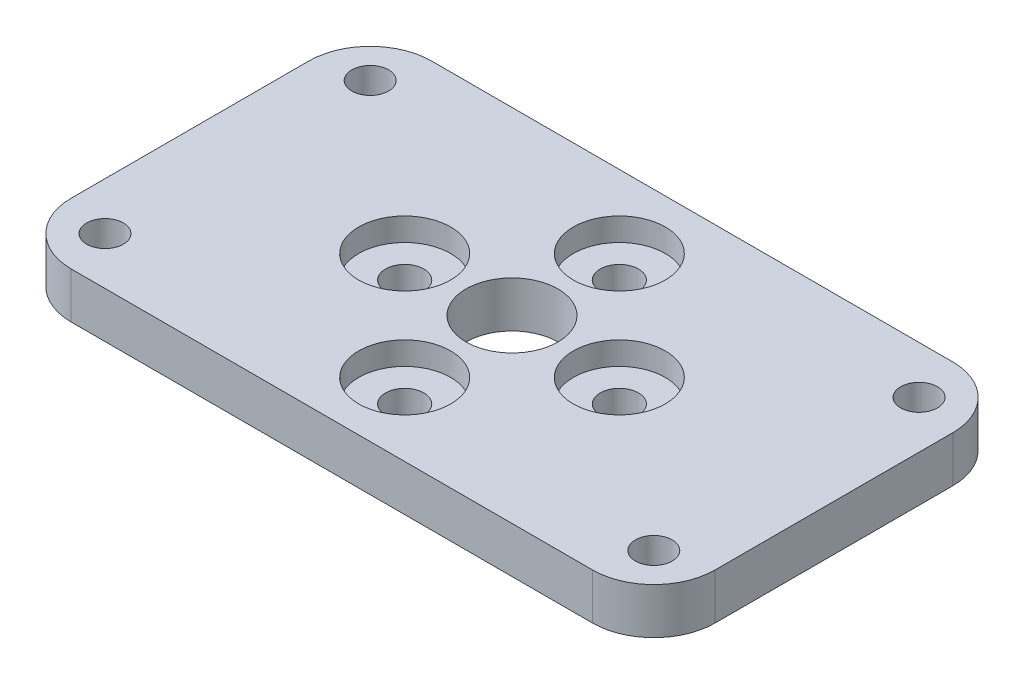
SolidWorks part; units mm, degrees
ref_plane "前视基准面" through (0, 0, 0) normal (0, 0, 1) x (1, 0, 0)
ref_plane "上视基准面" through (0, 0, 0) normal (0, 1, 0) x (1, 0, 0)
ref_plane "右视基准面" through (0, 0, 0) normal (1, 0, 0) x (0, 0, -1)
other "Configuration Table"
sketch "草图1" plane through (0, 0, 0) normal (0, 1, 0) x (1, 0, 0)
  line L0 (-13.2993, 0) -> (13.5934, 0) construction
  line L1 (0, 16.6571) -> (0, -12.7411) construction
  line L3 (21, -11.75) -> (-21, -11.75)
  line L4 (21, -11.75) -> (21, 11.75)
  line L5 (21, 11.75) -> (-21, 11.75)
  line L6 (-21, -11.75) -> (-21, 11.75)
  line L7 (21, -11.75) -> (-21, 11.75) construction
  line L8 (21, 11.75) -> (-21, -11.75) construction
  circle A0 centre (0, 0) radius 7 construction
  circle A1 centre (7, 0) radius 1.25
  circle A2 centre (0, -7) radius 1.25
  circle A3 centre (-7, 0) radius 1.25
  circle A4 centre (0, 7) radius 1.25
  circle A5 centre (-17.9, 8.65) radius 1.2
  circle A6 centre (17.9, 8.65) radius 1.2
  circle A7 centre (-17.9, -8.65) radius 1.2
  circle A8 centre (17.9, -8.65) radius 1.2
  circle A9 centre (0, 0) radius 3
  point P18 (0, 0)
  dimension "D1" = 14
  dimension "D2" = 2.5
  dimension "D4" = 35.8
  dimension "D5" = 17.3
  dimension "D6" = 2.4
  dimension "D7" = 42
  dimension "D8" = 23.5
  dimension "D3" = 4
extrude "凸台-拉伸1" add sketch "草图1" along normal blind 3
fillet "圆角1" radius 4 4 edges at (-21, 1.5, -11.75) (-21, 1.5, 11.75) (21, 1.5, 11.75) (21, 1.5, -11.75)
sketch "草图2" plane through (0, 3, 0) normal (0, 1, 0) x (1, 0, 0)
  circle A0 centre (7, 0) radius 3
  circle A1 centre (0, -7) radius 3
  circle A2 centre (-7, 0) radius 3
  circle A3 centre (0, 7) radius 3
  point P12 (0, 0)
  dimension "D1" = 6
  dimension "D2" = 4
extrude "切除-拉伸1" cut sketch "草图2" against normal blind 1.5
